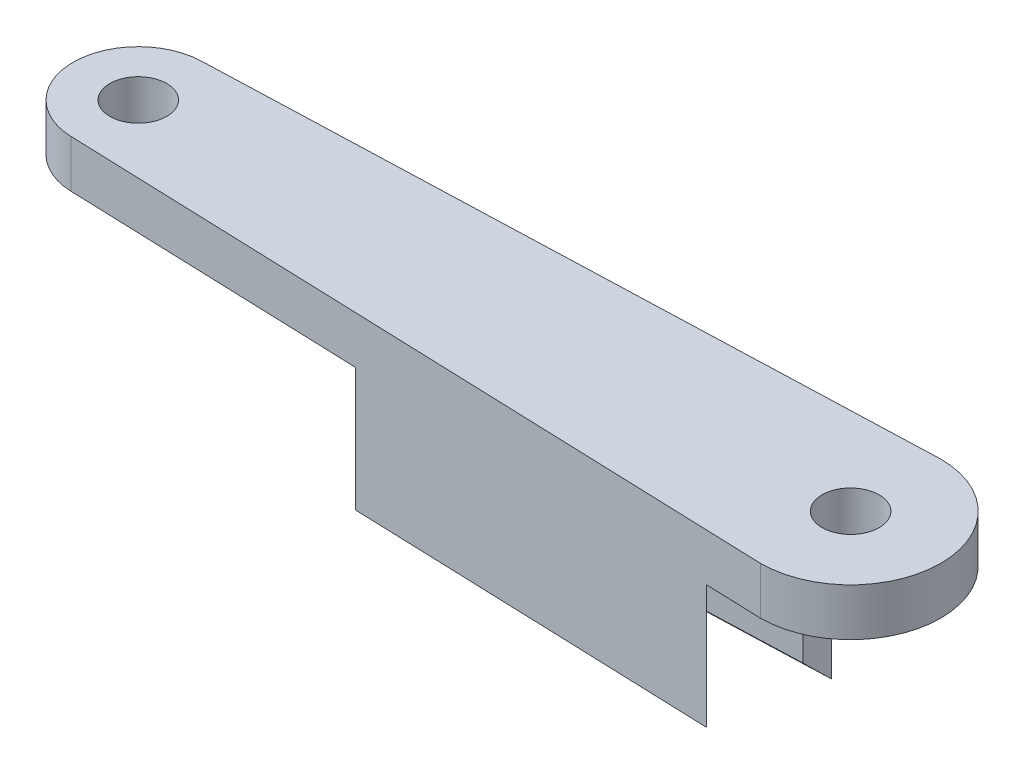
SolidWorks part; units mm, degrees
ref_plane "Front Plane" through (0, 0, 0) normal (0, 0, 1) x (1, 0, 0)
ref_plane "Top Plane" through (0, 0, 0) normal (0, 1, 0) x (1, 0, 0)
ref_plane "Right Plane" through (0, 0, 0) normal (1, 0, 0) x (0, 0, -1)
sketch "Sketch1" plane through (0, 0, 0) normal (0, 1, 0) x (1, 0, 0)
  circle A0 centre (0, 0) radius 6
  circle A1 centre (0, 0) radius 12
extrude "Boss-Extrude1" add sketch "Sketch1" against normal blind 10
sketch "Sketch2" plane through (0, 0, 0) normal (0, 1, 0) x (1, 0, 0)
  line L0 (0, 0) -> (-200, 0) construction
  line L1 (-200, 12) -> (0, 19)
  line L2 (-200, -12) -> (0, -19)
  arc A0 (-1.3284, -18.9535) -> (-1.3284, 18.9535) centre (0, 0) ccw
  arc A1 (-200, 12) -> (-200, -12) centre (-200, 0) ccw
  circle A2 centre (0, 0) radius 12
  circle A3 centre (-200, 0) radius 6
extrude "Boss-Extrude3" add sketch "Sketch2" against normal blind 10
sketch "Sketch3" plane through (0, -10, 0) normal (0, -1, 0) x (1, 0, 0)
  line L1 (-191.4152, -12.3005) -> (-11.7678, -18.5881)
  line L2 (-186.9841, -7.4556) -> (-17.4566, -13.389)
  line L4 (-0.9788, 13.9657) -> (0, 14)
  line L5 (-0.9788, -13.9657) -> (0, -14)
  line L6 (-0.6642, -18.9768) -> (0, -19)
  line L7 (-200, 0) -> (0, 0) construction
  line L8 (-186.9841, 7.4556) -> (-17.4566, 13.389)
  line L9 (-191.4152, 12.3005) -> (-11.7678, 18.5881)
  circle A2 centre (-200, 0) radius 7 construction
  circle A3 centre (0, 0) radius 14 construction
  arc A6 (-191.4152, -12.3005) -> (-186.9841, -7.4556) centre (-200, 0) ccw
  arc A9 (-17.4566, -13.389) -> (-11.7678, -18.5881) centre (0, 0) ccw
  arc A10 (-17.4566, 13.389) -> (-11.7678, 18.5881) centre (0, 0) cw
  arc A11 (-191.4152, 12.3005) -> (-186.9841, 7.4556) centre (-200, 0) cw
extrude "Boss-Extrude4" add sketch "Sketch3" along normal blind 26
sketch "Sketch5" plane through (0, -10, 0) normal (0, -1, 0) x (1, 0, 0)
  line L0 (0, 0) -> (-136.2584, 0) construction
  line L1 (-200, 12) -> (-150, 13.7416)
  line L2 (-200, -12) -> (-150, -13.7416)
  arc A1 (-150, 13.7416) -> (-150, -13.7416) centre (-150, 0) ccw
  arc A2 (-200, 12) -> (-200, -12) centre (-200, 0) ccw
sketch "Sketch6" plane through (0, -36, 0) normal (0, -1, 0) x (1, 0, 0)
  line L0 (-200, 12) -> (-191.4152, 12.3005) construction
  line L1 (-200, 12) -> (-191.4152, 12.3005)
  line L2 (-11.7678, 18.5881) -> (-191.4152, 12.3005) construction
  line L3 (-150.4807, 13.7332) -> (-191.4152, 12.3005)
  line L4 (-200, -12) -> (-191.4152, -12.3005) construction
  line L5 (-200, -12) -> (-191.4152, -12.3005)
  line L6 (-191.4152, -12.3005) -> (-11.7678, -18.5881) construction
  line L7 (-191.4152, -12.3005) -> (-150.4807, -13.7332)
  arc A0 (-150.4807, 13.7332) -> (-150.4807, -13.7332) centre (-150, 0) ccw
  arc A1 (-200, 12) -> (-200, -12) centre (-200, 0) ccw
extrude "Cut-Extrude3" cut sketch "Sketch6" against normal blind 41
sketch "Sketch7" plane through (0, -10, 0) normal (0, -1, 0) x (1, 0, 0)
  circle A0 centre (-150, 0) radius 6
extrude "Cut-Extrude4" cut sketch "Sketch7" against normal up to next
sketch "Sketch8" plane through (0, -36, 0) normal (0, -1, 0) x (-1, 0, 0)
  circle A0 centre (150, 0) radius 22
extrude "Cut-Extrude5" cut sketch "Sketch8" against normal blind 26
sketch "Sketch10" plane through (-0.4894, 0, -13.9829) normal (0.035, 0, 0.9994) x (0.9994, 0, -0.035)
  line L1 (-128.4346, -26) -> (-16.9776, -26)
  line L2 (-16.9776, -36) -> (-16.9776, -26)
  line L4 (-128.4346, -46) -> (-16.9776, -46)
  line L5 (-16.9776, -46) -> (-16.9776, -36)
  line L6 (-128.4346, -26) -> (-128.4346, -46)
extrude "Boss-Extrude5" add sketch "Sketch10" along normal blind 3
chamfer "Chamfer1" distance 3 angle 45 3 edges at (-17.3517, -36, -10.3909) (-73.0461, -46, -8.4415) (-128.7405, -36, -6.4922)
sketch "Sketch12" plane through (0, 0, 0) normal (0, 0, 1) x (1, 0, 0)
  line L0 (-128.8454, -46) -> (-17.4566, -46) construction
  line L1 (-133.3107, -10) -> (-88.3107, -10)
  line L2 (-133.3107, -10) -> (-133.3107, -46)
  line L3 (-133.3107, -46) -> (-88.3107, -46)
  line L4 (-88.3107, -10) -> (-88.3107, -46)
  dimension "D1" = 45
extrude "Cut-Extrude7" cut sketch "Sketch12" against normal through all and the other way through all
